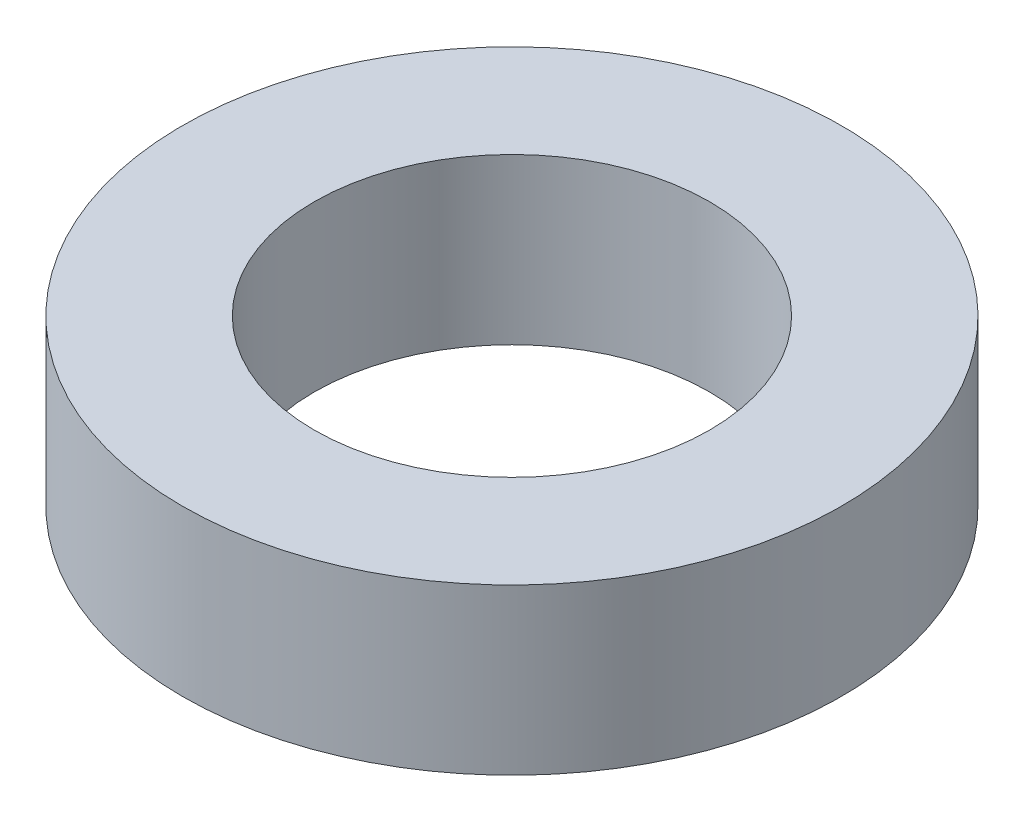
SolidWorks part; units mm, degrees
ref_plane "Front Plane" through (0, 0, 0) normal (0, 0, 1) x (1, 0, 0)
ref_plane "Top Plane" through (0, 0, 0) normal (0, 1, 0) x (1, 0, 0)
ref_plane "Right Plane" through (0, 0, 0) normal (1, 0, 0) x (0, 0, -1)
sketch "Sketch1" plane through (0, 0, 0) normal (0, 1, 0) x (1, 0, 0)
  circle A0 centre (0, 0) radius 50
  dimension "FLANGE_OD" = 100
extrude "Boss-Extrude1" add sketch "Sketch1" along normal blind 25
sketch "Sketch2" plane through (0, 0, 0) normal (0, 1, 0) x (1, 0, 0)
  circle A0 centre (0, 0) radius 30
  dimension "BORE_D" = 60
extrude "Cut-Extrude1" cut sketch "Sketch2" along normal through all
sketch "Sketch3" plane through (0, 25, 0) normal (0, 1, 0) x (1, 0, 0)
  circle A0 centre (0, 0) radius 21.4242 construction
  circle A1 centre (-21.4242, 0) radius 1.9983
  dimension "BOLT_D" = 3.9966
  dimension "BOLT_PCD" = 42.8485
extrude "Cut-Extrude2" cut sketch "Sketch3" against normal blind 23.0978 rebuild error yes
pattern_circular "CirPattern1" count 6 over 360 rebuild error yes
